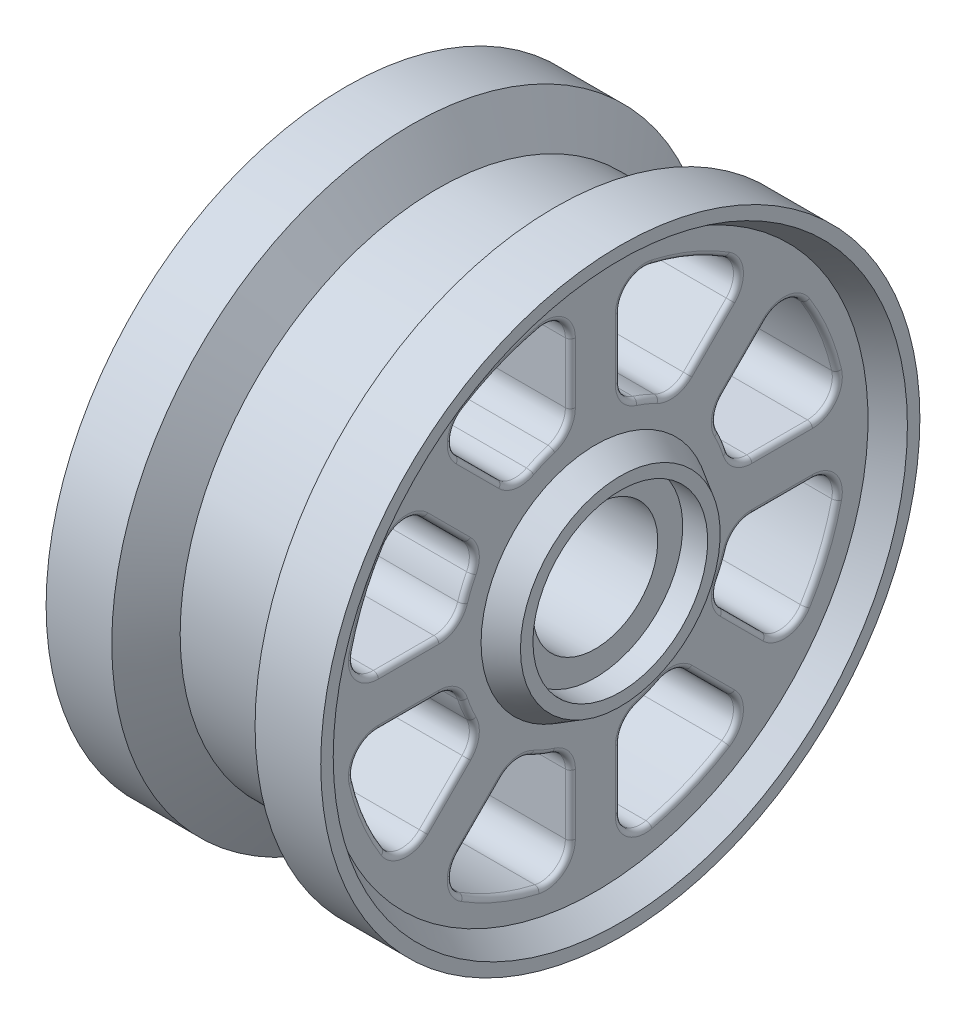
SolidWorks part; units mm, degrees
material "ABS"
ref_plane "Front" through (0, 0, 0) normal (0, 0, 1) x (1, 0, 0)
ref_plane "Top" through (0, 0, 0) normal (0, 1, 0) x (1, 0, 0)
ref_plane "Right" through (0, 0, 0) normal (1, 0, 0) x (0, 0, -1)
sketch "Sketch1" plane through (0, 0, 0) normal (0, 0, 1) x (1, 0, 0)
  line L0 (0, 0) -> (40.2325, 0) construction
  line L1 (0, 0) -> (0, 28.3421) construction
  line L2 (-0.915, 5.15) -> (0.915, 5.15)
  line L3 (0.915, 5.15) -> (1.435, 6)
  line L4 (1.435, 6) -> (2.75, 6)
  line L5 (2.75, 6) -> (2.75, 5.75)
  line L6 (2.75, 5.75) -> (2.25, 5.4613)
  line L7 (2.25, 5.4613) -> (2.25, 2.2887)
  line L9 (2.25, 2.2887) -> (2.75, 2)
  line L10 (2.75, 2) -> (2.75, 1.75)
  line L11 (2.75, 1.75) -> (2.25, 1.75)
  line L12 (2.25, 1.75) -> (2.25, 1.25)
  line L13 (2.25, 1.25) -> (-2.25, 1.25)
  line L14 (-2.25, 1.75) -> (-2.25, 1.25)
  line L15 (-2.75, 1.75) -> (-2.25, 1.75)
  line L16 (-2.75, 2) -> (-2.75, 1.75)
  line L17 (-2.25, 2.2887) -> (-2.75, 2)
  line L18 (-2.25, 5.4613) -> (-2.25, 2.2887)
  line L19 (-2.75, 5.75) -> (-2.25, 5.4613)
  line L20 (-2.75, 6) -> (-2.75, 5.75)
  line L21 (-1.435, 6) -> (-2.75, 6)
  line L22 (-0.915, 5.15) -> (-1.435, 6)
  point P19 (2.25, 1.5)
  point P25 (0, 1.25)
  point P34 (0, 5.15)
  dimension "D1" = 1.83
  dimension "D2" = 2.87
  dimension "D3" = 5.5
  dimension "D4" = 10.3
  dimension "D5" = 12
  dimension "D6" = 30
  dimension "D7" = 0.5
  dimension "D8" = 2.5
  dimension "D9" = 0.25
  dimension "D10" = 60
  dimension "D11" = 0.5
  dimension "D12" = 0.25
revolve "Revolve1" add sketch "Sketch1" angle 360 about L0
sketch "Sketch2" plane through (2.25, 0, 0) normal (1, 0, 0) x (0, 0, -1)
  line L0 (2.5696, 1.8625) -> (3.427, 2.7198)
  line L1 (0, 0) -> (0, 7.759) construction
  line L2 (3.134, 0.5) -> (4.3464, 0.5)
  line L3 (0, 0) -> (9.3708, 0) construction
  line L4 (0, 0) -> (7.0286, 7.0286) construction
  arc A4 (4.8337, 1.1121) -> (4.2043, 2.6316) centre (0, 0) ccw
  arc A5 (2.6577, 0.848) -> (2.4789, 1.2796) centre (0, 0) ccw
  arc A6 (2.6577, 0.848) -> (3.134, 0.5) centre (3.134, 1) ccw
  arc A7 (4.3464, 0.5) -> (4.8337, 1.1121) centre (4.3464, 1) ccw
  arc A8 (3.427, 2.7198) -> (4.2043, 2.6316) centre (3.7805, 2.3663) cw
  arc A9 (2.5696, 1.8625) -> (2.4789, 1.2796) centre (2.9232, 1.509) ccw
  circle A10 centre (0, 0) radius 2.2887 construction
  dimension "D1" = 4.96
  dimension "D2" = 2.7897
  dimension "D5" = 0.5
  dimension "D6" = 45
  dimension "D3" = 0.5
  dimension "D4" = 0.5
extrude "Cut-Extrude1" cut sketch "Sketch2" against normal up to surface (4.5 mm away) up to face at (-2.25, 0, 2.2887)
pattern_circular "CirPattern1" count 8 over 360 about axis through (2.75, 0, 0) along (-1, 0, 0) of "Cut-Extrude1"
fillet "Fillet1" radius 0.1 128 edges at (2.25, 0.6886, -4.7376) (2.25, 1.8981, -4.5824) (2.25, 2.8631, -3.8369) (2.25, 2.2912, -2.9983) (2.25, 1.5859, -2.4291) (2.25, 1.0676, -2.5773) (2.25, 0.5963, -2.839) (2.25, 0.5, -3.7402) (2.25, 3.8369, -2.8631) (2.25, 4.5824, -1.8981) (2.25, 4.7376, -0.6886) (2.25, 3.7402, -0.5) (2.25, 2.839, -0.5963) (2.25, 2.5773, -1.0676) (2.25, 2.4291, -1.5859) (2.25, 2.9983, -2.2912) (2.25, 2.8631, 3.8369) (2.25, 1.8981, 4.5824) (2.25, 0.6886, 4.7376) (2.25, 0.5, 3.7402) (2.25, 0.5963, 2.839) (2.25, 1.0676, 2.5773) (2.25, 1.5859, 2.4291) (2.25, 2.2912, 2.9983) (2.25, 4.7376, 0.6886) (2.25, 4.5824, 1.8981) (2.25, 3.8369, 2.8631) (2.25, 2.9983, 2.2912) (2.25, 2.4291, 1.5859) (2.25, 2.5773, 1.0676) (2.25, 2.839, 0.5963) (2.25, 3.7402, 0.5) (-2.25, 1.5859, -2.4291) (-2.25, 2.2912, -2.9983) (-2.25, 2.8631, -3.8369) (-2.25, 1.8981, -4.5824) (-2.25, 0.6886, -4.7376) (-2.25, 0.5, -3.7402) (-2.25, 0.5963, -2.839) (-2.25, 1.0676, -2.5773) (-2.25, -0.5963, -2.839) (-2.25, -0.5, -3.7402) (-2.25, -0.6886, -4.7376) (-2.25, -1.8981, -4.5824) (-2.25, -2.8631, -3.8369) (-2.25, -2.2912, -2.9983) (-2.25, -1.5859, -2.4291) (-2.25, -1.0676, -2.5773) (-2.25, 2.839, -0.5963) (-2.25, 3.7402, -0.5) (-2.25, 4.7376, -0.6886) (-2.25, 4.5824, -1.8981) (-2.25, 3.8369, -2.8631) (-2.25, 2.9983, -2.2912) (-2.25, 2.4291, -1.5859) (-2.25, 2.5773, -1.0676) (-2.25, 2.4291, 1.5859) (-2.25, 2.9983, 2.2912) (-2.25, 3.8369, 2.8631) (-2.25, 4.5824, 1.8981) (-2.25, 4.7376, 0.6886) (-2.25, 3.7402, 0.5) (-2.25, 2.839, 0.5963) (-2.25, 2.5773, 1.0676) (-2.25, -2.4291, -1.5859) (-2.25, -2.9983, -2.2912) (-2.25, -3.8369, -2.8631) (-2.25, -4.5824, -1.8981) (-2.25, -4.7376, -0.6886) (-2.25, -3.7402, -0.5) (-2.25, -2.839, -0.5963) (-2.25, -2.5773, -1.0676) (-2.25, -2.839, 0.5963) (-2.25, -3.7402, 0.5) (-2.25, -4.7376, 0.6886) (-2.25, -4.5824, 1.8981) (-2.25, -3.8369, 2.8631) (-2.25, -2.9983, 2.2912) (-2.25, -2.4291, 1.5859) (-2.25, -2.5773, 1.0676) (-2.25, -1.5859, 2.4291) (-2.25, -2.2912, 2.9983) (-2.25, -2.8631, 3.8369) (-2.25, -1.8981, 4.5824) (-2.25, -0.6886, 4.7376) (-2.25, -0.5, 3.7402) (-2.25, -0.5963, 2.839) (-2.25, -1.0676, 2.5773) (-2.25, 0.5963, 2.839) (-2.25, 0.5, 3.7402) (-2.25, 0.6886, 4.7376) (-2.25, 1.8981, 4.5824) (-2.25, 2.8631, 3.8369) (-2.25, 2.2912, 2.9983) (-2.25, 1.5859, 2.4291) (-2.25, 1.0676, 2.5773) (2.25, -1.8981, -4.5824) (2.25, -2.8631, -3.8369) (2.25, -2.2912, -2.9983) (2.25, -1.5859, -2.4291) (2.25, -1.0676, -2.5773) (2.25, -0.5963, -2.839) (2.25, -0.5, -3.7402) (2.25, -4.5824, -1.8981) (2.25, -4.7376, -0.6886) (2.25, -3.7402, -0.5) (2.25, -2.839, -0.5963) (2.25, -2.5773, -1.0676) (2.25, -2.4291, -1.5859) (2.25, -2.9983, -2.2912) (2.25, -4.5824, 1.8981) (2.25, -3.8369, 2.8631) (2.25, -2.9983, 2.2912) (2.25, -2.4291, 1.5859) (2.25, -2.5773, 1.0676) (2.25, -2.839, 0.5963) (2.25, -3.7402, 0.5) (2.25, -1.0676, 2.5773) (2.25, -1.5859, 2.4291) (2.25, -2.2912, 2.9983) (2.25, -2.8631, 3.8369) (2.25, -1.8981, 4.5824) (2.25, -0.6886, 4.7376) (2.25, -0.5, 3.7402) (2.25, -0.6886, -4.7376) (2.25, -3.8369, -2.8631) (2.25, -4.7376, 0.6886) (2.25, -0.5963, 2.839)
